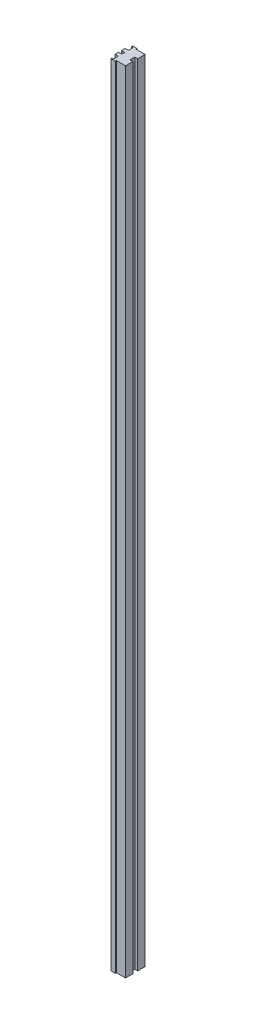
SolidWorks part; units mm, degrees
ref_plane "Спереди" through (0, 0, 0) normal (0, 0, 1) x (1, 0, 0)
ref_plane "Сверху" through (0, 0, 0) normal (0, 1, 0) x (1, 0, 0)
ref_plane "Справа" through (0, 0, 0) normal (1, 0, 0) x (0, 0, -1)
sketch "Эскиз1" plane through (0, 0, 0) normal (0, 1, 0) x (1, 0, 0)
  line L4 (-13.591, -14.9124) -> (-13.591, -7.6788)
  line L5 (-13.591, -7.6788) -> (-18.6478, -7.6788)
  line L6 (-18.6478, -7.6788) -> (-18.6478, -2.1842)
  line L7 (-18.9883, 0) -> (46.2952, 0) construction
  line L8 (-18.6478, -2.1842) -> (-13.591, -2.1842)
  line L13 (4.4514, -14.9124) -> (4.4514, -3.6855)
  line L14 (4.4514, -3.6855) -> (0, -3.6855)
  line L15 (0, -3.6855) -> (0, 3.6855)
  line L16 (-13.591, -2.1842) -> (-13.591, 2.1842)
  line L17 (-13.591, -14.9124) -> (-16.1194, -14.9124)
  line L18 (-16.1194, -14.9124) -> (-16.1194, -16.5497)
  line L19 (-16.1194, -16.5497) -> (-9.2579, -16.5497)
  line L20 (-9.2579, -16.5497) -> (-9.2579, -14.9124)
  line L21 (-9.2579, -14.9124) -> (4.4514, -14.9124)
  line L22 (-9.2579, 14.9124) -> (4.4514, 14.9124)
  line L23 (-9.2579, 16.5497) -> (-9.2579, 14.9124)
  line L24 (-16.1194, 16.5497) -> (-9.2579, 16.5497)
  line L25 (-16.1194, 14.9124) -> (-16.1194, 16.5497)
  line L26 (-13.591, 14.9124) -> (-16.1194, 14.9124)
  line L27 (4.4514, 3.6855) -> (0, 3.6855)
  line L28 (4.4514, 14.9124) -> (4.4514, 3.6855)
  line L29 (-18.6478, 2.1842) -> (-13.591, 2.1842)
  line L30 (-18.6478, 7.6788) -> (-18.6478, 2.1842)
  line L31 (-13.591, 7.6788) -> (-18.6478, 7.6788)
  line L32 (-13.591, 14.9124) -> (-13.591, 7.6788)
  point P21 (0, 0)
  point P25 (-13.591, 0)
  point P26 (0, 0)
extrude "Бобышка-Вытянуть1" add sketch "Эскиз1" along normal blind 1200
